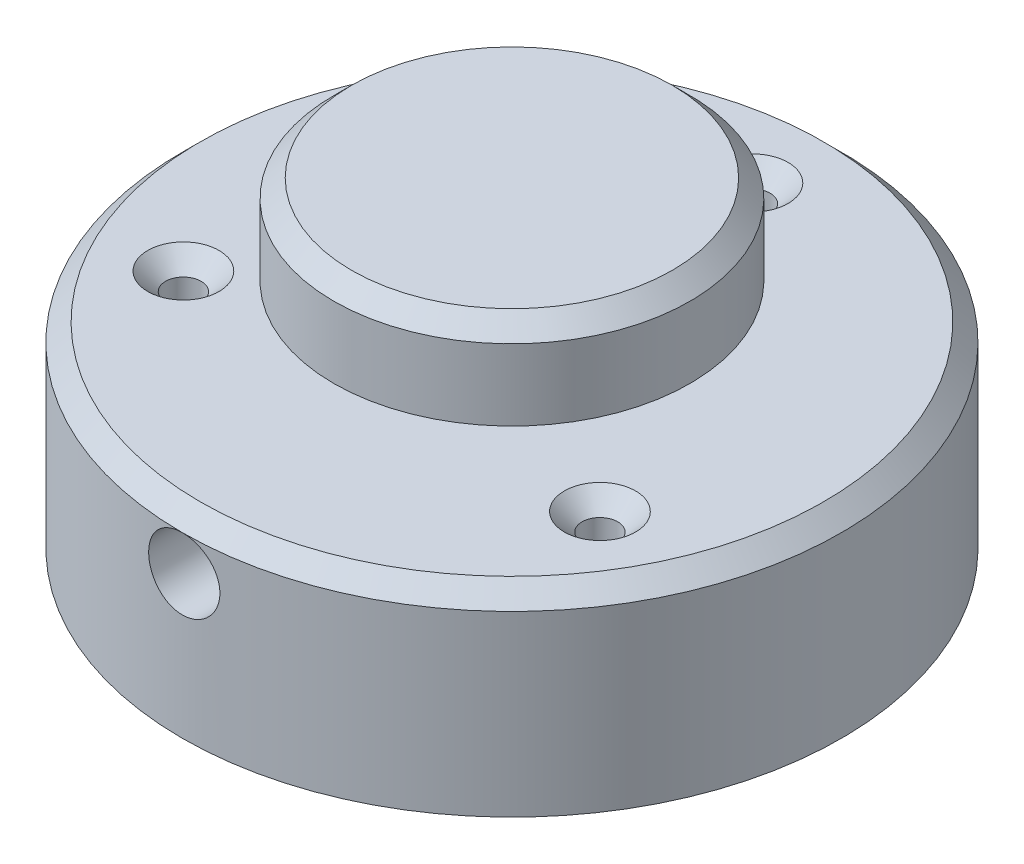
SolidWorks part; units mm, degrees
ref_plane "Front Plane" through (0, 0, 0) normal (0, 0, 1) x (1, 0, 0)
ref_plane "Top Plane" through (0, 0, 0) normal (0, 1, 0) x (1, 0, 0)
ref_plane "Right Plane" through (0, 0, 0) normal (1, 0, 0) x (0, 0, -1)
sketch "Sketch2" plane through (0, 0, 0) normal (0, 1, 0) x (1, 0, 0)
  line L0 (0, -13.5) -> (0, 13.5) construction
  line L1 (-11.6913, -6.75) -> (11.6913, 6.75) construction
  line L2 (-11.6913, 6.75) -> (11.6913, -6.75) construction
  circle A0 centre (0, 0) radius 18.5
  circle A1 centre (0, 13.5) radius 1
  circle A2 centre (0, -13.5) radius 1 construction
  circle A3 centre (-11.6913, 6.75) radius 1 construction
  circle A4 centre (-11.6913, -6.75) radius 1
  circle A5 centre (11.6913, -6.75) radius 1
  circle A6 centre (11.6913, 6.75) radius 1 construction
  circle A7 centre (0, 0) radius 13.5 construction
  point P6 (0, 0)
  point P11 (0, 0)
  point P14 (0, 0)
  dimension "D1" = 37
  dimension "D2" = 60
  dimension "D4" = 2
  dimension "D3" = 60
  dimension "D5" = 27
extrude "Boss-Extrude1" add sketch "Sketch2" along normal blind 11
sketch "Sketch4" plane through (0, 11, 0) normal (0, 1, 0) x (1, 0, 0)
  circle A0 centre (0, 0) radius 5
  dimension "D1" = 10
extrude "Boss-Extrude3" add sketch "Sketch4" along normal blind 2
sketch "Sketch5" plane through (0, 13, 0) normal (0, 1, 0) x (1, 0, 0)
  circle A0 centre (0, 0) radius 10
extrude "Boss-Extrude4" add sketch "Sketch5" along normal blind 5
fillet "Fillet1" radius 1 2 edges at (0, 13, 5) (0, 11, 5)
chamfer "Chamfer3" distance 1 angle 45 3 edges at (11.6913, 11, 7.75) (-11.6913, 11, 7.75) (0, 11, -12.5)
chamfer "Chamfer4" distance 1 angle 45 2 edges at (0, 11, 18.5) (0, 18, 10)
sketch "Sketch6" plane through (0, 0, 0) normal (0, 0, 1) x (1, 0, 0)
  line L0 (0, 0) -> (0, 11) construction
  line L2 (17.5, 11) -> (-17.5, 11) construction
  circle A0 centre (0, 8) radius 2
  point P3 (0, 0)
  point P5 (0, 7.4697)
  dimension "D2" = 4
  dimension "D1" = 3
extrude "Cut-Extrude1" cut sketch "Sketch6" against normal blind 25 from offset 20
